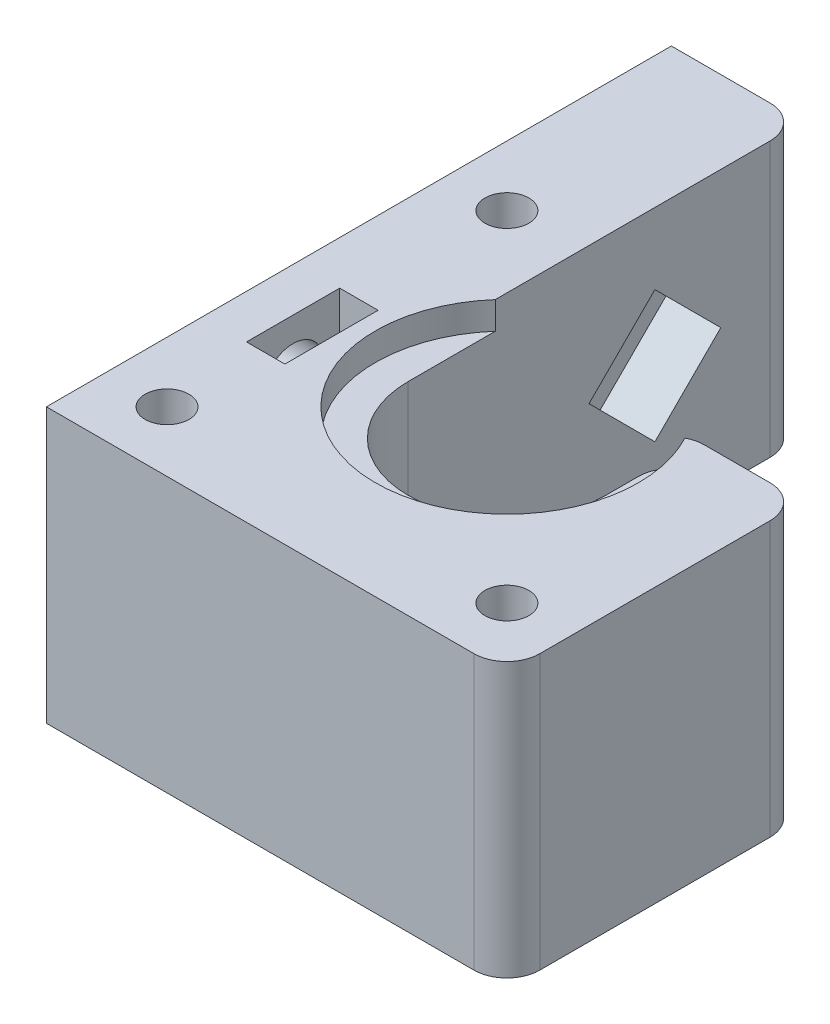
SolidWorks part; units mm, degrees
ref_plane "Front Plane" through (0, 0, 0) normal (0, 0, 1) x (1, 0, 0)
ref_plane "Top Plane" through (0, 0, 0) normal (0, 1, 0) x (1, 0, 0)
ref_plane "Right Plane" through (0, 0, 0) normal (1, 0, 0) x (0, 0, -1)
sketch "Sketch1" plane through (0, 0, 0) normal (0, 1, 0) x (1, 0, 0)
  line L0 (0, 0) -> (0, 21) construction
  line L1 (-21, -21) -> (21, -21)
  line L2 (-21, -21) -> (-21, 21)
  line L3 (-21, 21) -> (-9, 21)
  line L4 (21, -21) -> (21, 21)
  line L5 (-21, -21) -> (-6.364, -6.364) construction
  line L6 (-21, 21) -> (-9, 9) construction
  line L7 (9, 0) -> (9, 21)
  line L8 (-9, 0) -> (-9, 21)
  line L9 (9, 21) -> (21, 21)
  line L10 (6.364, -6.364) -> (21, -21) construction
  line L11 (9, 9) -> (21, 21) construction
  line L12 (9, 0) -> (9, 21) construction
  line L13 (-9, 0) -> (-9, 21) construction
  arc A0 (-9, 0) -> (9, 0) centre (0, 0) ccw
  circle A1 centre (-15.5, 15.5) radius 2
  circle A2 centre (15.5, 15.5) radius 2
  circle A3 centre (15.5, -15.5) radius 2
  circle A4 centre (-15.5, -15.5) radius 2
  point P0 (0, 0)
  point P19 (0, 0)
  dimension "D1" = 18
  dimension "D3" = 4
  dimension "D2" = 42
  dimension "D4" = 15.5
  dimension "D6" = 18
  dimension "D5" = 4
extrude "Boss-Extrude1" add sketch "Sketch1" along normal blind 25 contours A0 L8 L3 L2 L1 L4 L9 L7 A4 A3 A2 A1 region at (-20.406, 0, 0)
sketch "Sketch4" plane through (-21, 0, 0) normal (-1, 0, 0) x (0, 0, 1)
  line L0 (21, 0) -> (-21, 0) construction
  line L1 (-21, 25) -> (-36, 25)
  line L2 (-21, 25) -> (-21, 0)
  line L3 (-21, 0) -> (-36, 0)
  line L4 (-36, 25) -> (-36, 0)
  dimension "D1" = 15
extrude "Boss-Extrude5" add sketch "Sketch4" against normal up to vertex (12 mm away) up to point (-9, 0, -21)
sketch "Sketch6" plane through (0, 0, 0) normal (0, -1, 0) x (1, 0, 0)
  line L0 (9, -21) -> (-9, -21)
  line L1 (-9, 0) -> (-9, -36) construction
  line L2 (-9, 0) -> (-9, -21)
  line L3 (9, 0) -> (9, -21)
  arc A0 (-9, 0) -> (9, 0) centre (0, 0) ccw
extrude "Boss-Extrude6" add sketch "Sketch6" against normal blind 3
sketch "Sketch7" plane through (-21, 0, 0) normal (-1, 0, 0) x (0, 0, 1)
  line L0 (-22.5, 12.5) -> (2.5, 12.5) construction
  line L3 (-5, 20) -> (10, 20) construction
  line L4 (-5, 22.75) -> (10, 22.75) construction
  line L5 (-5, 17.25) -> (10, 17.25) construction
  line L6 (-30, 12.5) -> (-15, 12.5) construction
  line L9 (-30, 15.25) -> (-15, 15.25) construction
  line L10 (-30, 9.75) -> (-15, 9.75) construction
  line L11 (-5, 5) -> (10, 5) construction
  line L12 (-5, 2.25) -> (10, 2.25) construction
  line L13 (-5, 7.75) -> (10, 7.75) construction
  line L14 (-7.5, 25) -> (-7.5, 0) construction
  line L15 (21, 25) -> (-36, 25) construction
  line L16 (21, 0) -> (-36, 0) construction
  line L17 (2.5, 20) -> (2.5, 5) construction
  arc A0 (-5, 22.75) -> (-5, 17.25) centre (-5, 20) ccw construction
  arc A1 (10, 17.25) -> (10, 22.75) centre (10, 20) ccw construction
  arc A4 (-30, 15.25) -> (-30, 9.75) centre (-30, 12.5) ccw construction
  arc A5 (-15, 9.75) -> (-15, 15.25) centre (-15, 12.5) ccw construction
  arc A6 (-5, 2.25) -> (-5, 7.75) centre (-5, 5) cw construction
  arc A7 (10, 7.75) -> (10, 2.25) centre (10, 5) cw construction
  circle A8 centre (-22.5, 12.5) radius 2.75
  circle A9 centre (2.5, 20) radius 2.75
  circle A10 centre (2.5, 5) radius 2.75
  point P2 (-7.5, 12.5)
  point P8 (2.5, 20)
  point P15 (-22.5, 12.5)
  point P22 (2.5, 5)
  dimension "D3" = 2.75
  dimension "D4" = 15
  dimension "D1" = 15
  dimension "D2" = 25
  dimension "D5" = 15
extrude "Cut-Extrude3" cut sketch "Sketch7" against normal blind 7.5
sketch "Sketch10" plane through (-9, 0, 0) normal (1, 0, 0) x (0, 0, -1)
  line L1 (16.4896, 12.5) -> (22.5, 6.4896)
  line L2 (16.4896, 12.5) -> (22.5, 18.5104)
  line L3 (22.5, 18.5104) -> (28.5104, 12.5)
  line L4 (22.5, 6.4896) -> (28.5104, 12.5)
  line L5 (16.4896, 12.5) -> (28.5104, 12.5) construction
  line L6 (22.5, 18.5104) -> (22.5, 6.4896) construction
  circle A0 centre (22.5, 12.5) radius 2.75 construction
  circle A1 centre (22.5, 12.5) radius 2.75 construction
  dimension "D1" = 8.5
extrude "Cut-Extrude5" cut sketch "Sketch10" against normal blind 5
sketch "Sketch11" plane through (-13.5, 0, 0) normal (-1, 0, 0) x (0, 0, 1)
  line L0 (21, 25) -> (-36, 25) construction
  line L1 (-1.75, 25) -> (6.75, 25)
  line L2 (-1.75, 25) -> (-1.75, 15)
  line L3 (-1.75, 0) -> (6.75, 0)
  line L4 (6.75, 25) -> (6.75, 15)
  line L5 (21, 0) -> (-36, 0) construction
  line L6 (-1.75, 10) -> (6.75, 10)
  line L7 (2.5, 10) -> (2.5, 5) construction
  line L8 (-1.75, 15) -> (6.75, 15)
  line L9 (2.5, 15) -> (2.5, 20) construction
  line L10 (-1.75, 15) -> (-1.75, 10) construction
  line L11 (-1.75, 10) -> (-1.75, 0)
  line L12 (6.75, 15) -> (6.75, 10) construction
  line L13 (6.75, 10) -> (6.75, 0)
  dimension "D1" = 5
  dimension "D2" = 8.5
extrude "Cut-Extrude6" cut sketch "Sketch11" along normal blind 3.5
fillet "Fillet2" radius 3 4 edges at (21, 12.5, -21) (-9, 1.5, -21) (-9, 12.5, -36) (9, 14, -21)
hole_wizard "CSK for M3 Cross Recess Flat Head Screw1" positions "Sketch12" profile "Sketch13" countersink size "M3" standard "IS" end condition through all
sketch "Sketch12" plane through (0, 0, 0) normal (0, -1, 0) x (-1, 0, 0)
  point P0 (-15.5, 15.5)
  point P3 (15.5, 15.5)
  point P6 (15.5, -15.5)
  point P9 (-15.5, -15.5)
sketch "Sketch13" plane through (15.5, 0, -15.5) normal (1, 0, 0) x (0, 0, -1)
  line L0 (0, 0) -> (0, 25)
  line L1 (0, 25) -> (1.8, 25)
  line L2 (1.8, 25) -> (1.8, 1.95)
  line L3 (1.8, 1.95) -> (3.75, 0)
  line L5 (3.75, 0) -> (0, 0)
  line L6 (-1.8, 1.95) -> (-3.75, 0) construction
  line L11 (0, -6.35) -> (0, 107.95) construction
  dimension "Thru Hole Dia." = 3.6
  dimension "Thru Hole Depth" = 25
  dimension "Near C'Sink Dia." = 7.5
  dimension "Near C'Sink Angle" = 90
sketch "Sketch16" plane through (0, 25, 0) normal (0, 1, 0) x (1, 0, 0)
  line L5 (-9, 24) -> (-9, 0)
  line L6 (-9, 0) -> (-9, 33) construction
  line L7 (-9, 0) -> (9, 0)
  line L8 (9, 0) -> (9, 6)
  line L10 (9, 6) -> (21, 6)
  line L11 (21, -21) -> (21, 18) construction
  line L12 (21, 6) -> (21, 24)
  line L13 (21, 24) -> (-9, 24)
  line L14 (12, 21) -> (18, 21) construction
  arc A2 (-9, 24) -> (-6, 21) centre (-6, 24) ccw construction
  dimension "D1" = 15
extrude "Cut-Extrude9" cut sketch "Sketch16" against normal blind 33
fillet "Fillet4" radius 3 3 edges at (21, 12.5, -6) (9, 12.5, -6) (21, 12.5, 21)
sketch "Sketch17" plane through (0, 25, 0) normal (0, 1, 0) x (1, 0, 0)
  circle A0 centre (0, 0) radius 12
  dimension "D1" = 24
extrude "Cut-Extrude10" cut sketch "Sketch17" against normal blind 2.5
